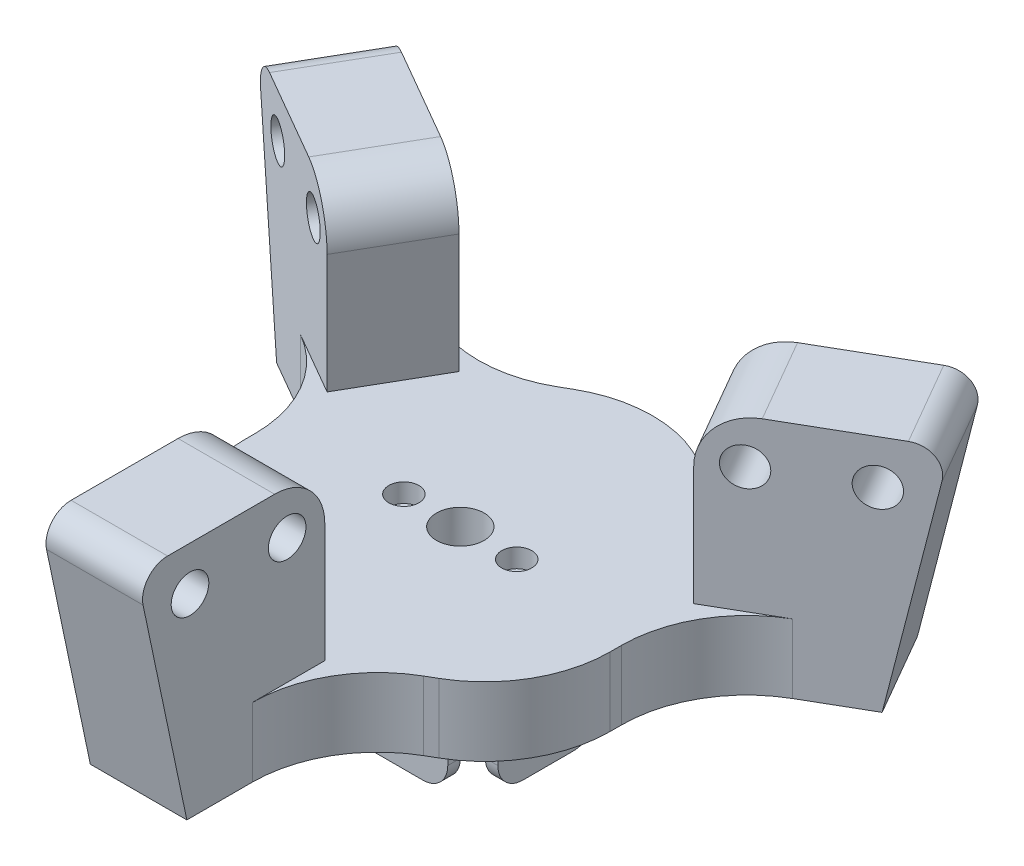
SolidWorks part; units mm, degrees
ref_plane "Piano frontale" through (0, 0, 0) normal (0, 0, 1) x (1, 0, 0)
ref_plane "Piano superiore" through (0, 0, 0) normal (0, 1, 0) x (1, 0, 0)
ref_plane "Piano destro" through (0, 0, 0) normal (1, 0, 0) x (0, 0, -1)
sketch "Schizzo1" plane through (0, 0, 0) normal (0, 1, 0) x (1, 0, 0)
  line L0 (0, -29.66) -> (0, 0) construction
  line L1 (-27.6113, 11.4958) -> (-14.6209, 3.9958)
  line L2 (-23.7613, 18.1642) -> (-27.6113, 11.4958)
  line L3 (-10.7709, 10.6642) -> (-23.7613, 18.1642)
  line L4 (-3.85, -14.66) -> (-3.85, -29.66)
  line L13 (-3.85, -29.66) -> (3.85, -29.66)
  line L14 (3.85, -29.66) -> (3.85, -14.66)
  line L15 (23.7613, 18.1642) -> (10.7709, 10.6642)
  line L16 (27.6113, 11.4958) -> (23.7613, 18.1642)
  line L17 (14.6209, 3.9958) -> (27.6113, 11.4958)
  line L29 (3.85, -14.66) -> (14.6209, -8.4414)
  line L51 (14.6209, -8.4414) -> (14.6209, 3.9958)
  line L52 (10.7709, 10.6642) -> (0, 16.8828)
  line L53 (0, 16.8828) -> (-10.7709, 10.6642)
  line L54 (-14.6209, 3.9958) -> (-14.6209, -8.4414)
  line L55 (-14.6209, -8.4414) -> (-3.85, -14.66)
  circle A1 centre (0, 0) radius 15.1571 construction
  circle A2 centre (0, 0) radius 2.5
  circle A3 centre (0, 0) radius 14.6209 construction
  point P14 (0, 0)
  dimension "D1" = 3
  dimension "D5" = 5
  dimension "D2" = 15
  dimension "D3" = 7.7
  dimension "D4" = 29.66
extrude "Boss extrusion" add sketch "Schizzo1" along normal blind 5.5 contours L14 L29 L51 L17 L16 L15 L52 L53 L3 L2 L1 L54 L55 L4 L13
sketch "Schizzo2" plane through (0, 5.5, 0) normal (0, 1, 0) x (1, 0, 0)
  line L19 (-23.7613, 18.1642) -> (-27.6113, 11.4958)
  line L20 (-27.6113, 11.4958) -> (-14.6209, 3.9958)
  line L21 (-14.6209, 3.9958) -> (-10.7709, 10.6642)
  line L22 (-10.7709, 10.6642) -> (-23.7613, 18.1642)
  line L23 (-3.85, -14.66) -> (-3.85, -29.66)
  line L24 (-3.85, -29.66) -> (3.85, -29.66)
  line L25 (3.85, -29.66) -> (3.85, -14.66)
  line L26 (3.85, -14.66) -> (-3.85, -14.66)
  line L27 (10.7709, 10.6642) -> (14.6209, 3.9958)
  line L28 (14.6209, 3.9958) -> (27.6113, 11.4958)
  line L29 (27.6113, 11.4958) -> (23.7613, 18.1642)
  line L30 (23.7613, 18.1642) -> (10.7709, 10.6642)
extrude "external extrusion" add sketch "Schizzo2" along normal blind 13.5
sketch "Schizzo3" plane through (0, 5.5, 0) normal (0, 1, 0) x (1, 0, 0)
  circle A0 centre (0, 0) radius 1.9
  dimension "D1" = 3.8
extrude "cetral hole" cut sketch "Schizzo3" against normal through all
sketch "Sketch1" plane through (-3.85, 0, 0) normal (-1, 0, 0) x (0, 0, 1)
  line L0 (29.66, 19) -> (29.66, 0)
  line L1 (29.66, 0) -> (25.66, 0)
  line L2 (14.66, 0) -> (29.66, 0) construction
  line L3 (25.66, 0) -> (29.66, 19)
  line L4 (14.66, 19) -> (14.66, 5.5) construction
  line L5 (14.66, 19) -> (29.66, 19) construction
  line L6 (17.66, 15.5) -> (25.41, 15.5) construction
  circle A0 centre (17.66, 15.5) radius 1.5
  circle A1 centre (25.41, 15.5) radius 1.5
  dimension "D2" = 3
  dimension "D1" = 4
  dimension "D3" = 7.75
  dimension "D4" = 3
  dimension "D5" = 3.5
extrude "Cut-Extrude1" cut sketch "Sketch1" against normal blind 7.7
pattern_circular "CirPattern1" count 3 every 120 about axis through (0, 5.5, 0) along (0, 1, 0) of "Cut-Extrude1"
fillet "Fillet1" radius 10 9 edges at (-10.7709, 2.75, -10.6642) (0, 2.75, -16.8828) (10.7709, 2.75, -10.6642) (14.6209, 2.75, -3.9958) (14.6209, 2.75, 8.4414) (3.85, 2.75, 14.66) (-3.85, 2.75, 14.66) (-14.6209, 2.75, 8.4414) (-14.6209, 2.75, -3.9958)
fillet "Fillet2" radius 4 3 edges at (12.6959, 19, -7.33) (0, 19, 14.66) (-12.6959, 19, -7.33)
fillet "Fillet3" radius 2 3 edges at (-25.6863, 19, -14.83) (25.6863, 19, -14.83) (0, 19, 29.66)
sketch "Sketch2" plane through (0, 0, 0) normal (0, -1, 0) x (1, 0, 0)
  line L0 (-9.4717, 0) -> (10.531, 0) construction
  line L2 (-6, -4) -> (-6, 4)
  line L3 (-5, 5) -> (5, 5)
  line L6 (-6, -4) -> (-7, -4)
  line L8 (-7, -4) -> (-7, 4)
  line L9 (-5, 6) -> (5, 6)
  line L17 (0, 6.6218) -> (0, -6.7332) construction
  line L22 (-6, 4) -> (-7, 4)
  line L24 (-5, 5) -> (-5, 6)
  line L25 (6, 4) -> (7, 4)
  line L28 (5, 5) -> (5, 6)
  line L30 (7, -4) -> (7, 4)
  line L31 (6, -4) -> (7, -4)
  line L32 (6, -4) -> (6, 4)
  line L33 (5, -5) -> (5, -6)
  line L34 (-5, -5) -> (-5, -6)
  line L35 (-5, -6) -> (5, -6)
  line L36 (-5, -5) -> (5, -5)
  line L38 (-6, -5) -> (6, -5)
  line L39 (-6, -5) -> (-6, 5)
  line L40 (-6, 5) -> (6, 5)
  line L41 (6, -5) -> (6, 5)
  line L42 (-6, -5) -> (6, 5) construction
  line L43 (-6, 5) -> (6, -5) construction
  circle A0 centre (-4.5, 0) radius 0.5
  circle A1 centre (4.5, 0) radius 0.5
  circle A2 centre (4.5, 0) radius 1.2
  circle A3 centre (-4.5, 0) radius 1.2
  point P0 (0, 0)
  point P6 (0, 0)
  point P25 (0, 0)
  circle M14 centre (0, 0) radius 1.9
  dimension "D1" = 1
  dimension "D9" = 2.4
  dimension "D2" = 9
  dimension "D3" = 1
  dimension "D4" = 6
  dimension "D5" = 1
  dimension "D6" = 8
  dimension "D7" = 10
  dimension "D8" = 5
extrude "Cut-Extrude2" cut sketch "Sketch2" against normal blind 7.7 contours A0 | A1 region at (-4.5, 0, 0) region at (4.5, 0, 0)
extrude "Boss-Extrude1" add sketch "Sketch2<5>" along normal blind 7.5 contours L32 L31 L30 L25 | L3 L28 L9 L24 | L2 L22 L8 L6 | L36 L34 L35 L33 region at (-6.5, 0, 0) region at (0, 0, -5.5) region at (0, 0, 5.5) region at (6.5, 0, 0)
sketch "Sketch2<5>" plane through (0, 0, 0) normal (0, -1, 0) x (1, 0, 0) same geometry as "Sketch2"
fillet "Fillet4" radius 2 8 edges at (5, -7.5, -5.5) (-5, -7.5, -5.5) (6.5, -7.5, 4) (6.5, -7.5, -4) (-5, -7.5, 5.5) (5, -7.5, 5.5) (-6.5, -7.5, 4) (-6.5, -7.5, -4)
chamfer "Chamfer1" distance 2 angle 45 4 edges at (0, 0, 6) (-7, 0, 0) (0, 0, -6) (7, 0, 0)
extrude "Cut-Extrude4" cut sketch "Sketch2<6>" against normal blind 1.5 contours L38 L41 L32 L40 L3 L39 L2 L36 A2 A3 M14 | A3 A0 | A2 A1 region at (-5.8438, 0, 0) region at (3.3339, 0, 0) region at (-5.6661, 0, 0)
sketch "Sketch2<6>" plane through (0, 0, 0) normal (0, -1, 0) x (1, 0, 0) same geometry as "Sketch2"
extrude "Cut-Extrude5" cut sketch "Sketch2<7>" along normal blind 1.5 from surface contours A3 A0 | A2 A1 region at (3.3339, 0, 0) region at (-5.6661, 0, 0) starting at face at (4.5, 5.5, 0.5)
sketch "Sketch2<7>" plane through (0, 0, 0) normal (0, -1, 0) x (1, 0, 0) same geometry as "Sketch2"
sketch "Sketch4" plane through (0, 1.5, 0) normal (0, -1, 0) x (1, 0, 0)
  circle A0 centre (0, 0) radius 2.5
  dimension "D1" = 5
extrude "Cut-Extrude6" cut sketch "Sketch4" against normal blind 0.7
